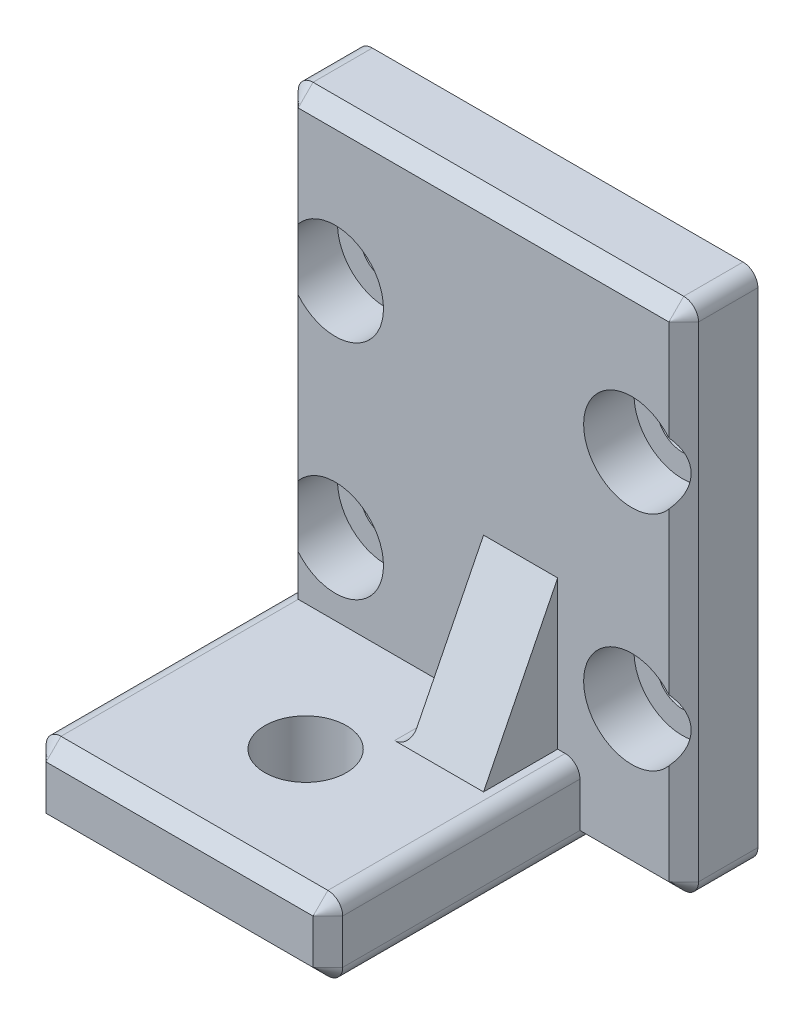
SolidWorks part; units mm, degrees
ref_plane "Front Plane" through (0, 0, 0) normal (0, 0, 1) x (1, 0, 0)
ref_plane "Top Plane" through (0, 0, 0) normal (0, 1, 0) x (1, 0, 0)
ref_plane "Right Plane" through (0, 0, 0) normal (1, 0, 0) x (0, 0, -1)
ref_plane "Rail Mount Front" through (0, 0, 5) normal (0, 0, 1) x (1, 0, 0)
ref_plane "ExtrusionMountFront" through (0, 0, 22) normal (0, 0, 1) x (1, 0, 0)
sketch "RailMountSketch" plane through (0, 0, 0) normal (0, 0, 1) x (1, 0, 0)
  line L1 (-13.5, 0) -> (13.5, 0)
  line L2 (-13.5, 0) -> (-13.5, 34.7)
  line L3 (-13.5, 34.7) -> (13.5, 34.7)
  line L4 (13.5, 0) -> (13.5, 34.7)
  line L5 (-10, 9.85) -> (10, 9.85) construction
  line L6 (-10, 9.85) -> (-10, 24.85) construction
  line L7 (-10, 24.85) -> (10, 24.85) construction
  line L8 (10, 9.85) -> (10, 24.85) construction
  line L9 (-10, 9.85) -> (10, 24.85) construction
  line L10 (-10, 24.85) -> (10, 9.85) construction
  line L11 (-13.5, 5) -> (6.5, 5) construction
  line L12 (-13.5, 5) -> (-13.5, 0) construction
  line L13 (-13.5, 0) -> (6.5, 0) construction
  line L14 (6.5, 5) -> (6.5, 0) construction
  line L15 (-13.5, 5) -> (6.5, 0) construction
  line L16 (-13.5, 0) -> (6.5, 5) construction
  point P4 (0, 17.35)
  point P12 (-3.5, 2.5)
  dimension "D1" = 27
  dimension "D2" = 34.7
  dimension "D3" = 20
  dimension "D4" = 15
  dimension "D5" = 17.35
  dimension "D6" = 20
  dimension "D7" = 6.5
  dimension "D8" = 5
extrude "Rail Mount" add sketch "RailMountSketch" along normal up to surface (5 mm away) up to plane "Rail Mount Front"
ref_plane "ExtrusionMountingTopPlane" through (0, 5, 0) normal (0, 1, 0) x (1, 0, 0)
hole_wizard "Rail Mounting Holes" positions "Sketch2" profile "Sketch3" counterbore size "M3" standard "ISO" end condition through all
sketch "Sketch2" plane through (0, 0, 5) normal (0, 0, 1) x (1, 0, 0)
  point P0 (-10, 24.85)
  point P3 (10, 24.85)
  point P6 (10, 9.85)
  point P9 (-10, 9.85)
sketch "Sketch3" plane through (-10, 24.85, 5) normal (1, 0, 0) x (0, -1, 0)
  line L0 (0, 0) -> (0, 5)
  line L1 (0, 5) -> (1.7, 5)
  line L3 (1.7, 5) -> (1.7, 3.4)
  line L4 (1.7, 3.4) -> (3.25, 3.4)
  line L5 (3.25, 3.4) -> (3.25, 0)
  line L7 (3.25, 0) -> (0, 0)
  line L11 (0, -6.35) -> (0, 107.95) construction
  dimension "Thru Hole Dia." = 3.4
  dimension "Thru Hole Depth" = 5
  dimension "C'Bore Dia." = 6.5
  dimension "C'Bore Depth" = 3.4
sketch "ExtrusionMountSketch" plane through (0, 0, 5) normal (0, 0, 1) x (1, 0, 0)
  line L1 (-13.5, 0) -> (13.5, 0) construction
  line L3 (-13.5, 5) -> (6.5, 5) construction
  line L4 (6.5, 5) -> (6.5, 0)
  line L5 (-13.5, 0) -> (6.5, 0)
  line L6 (-13.5, 5) -> (-13.5, 0)
  line L7 (-13.5, 5) -> (6.5, 5)
extrude "ExtrusionMount" add sketch "ExtrusionMountSketch" along normal up to surface (17 mm away) up to plane "ExtrusionMountFront"
sketch "ExtrusionMountingHolePosition" plane through (0, 5, 0) normal (0, 1, 0) x (1, 0, 0)
  line L0 (-3.5, -22) -> (-3.5, -5)
  line L3 (-13.6459, -5) -> (13.6459, -5) construction
  line L4 (-13.6459, -22) -> (13.6459, -22) construction
  line L5 (-13.5, 0) -> (6.5, 0) construction
  line L6 (-13.5, 0) -> (6.5, 0) construction
  point P0 (-3.5, -13.5)
  point P7 (-3.5, -13.5)
  dimension "D1" = 10
hole_wizard "ExtrusionMountingHole" positions "Sketch8" profile "Sketch9" hole size "M5" standard "ISO" end condition through all
sketch "Sketch8" plane through (0, 5, 0) normal (0, 1, 0) x (1, 0, 0)
  point P0 (-3.5, -13.5)
sketch "Sketch9" plane through (-3.5, 5, 13.5) normal (1, 0, 0) x (0, 0, 1)
  line L0 (0, 0) -> (0, 5)
  line L1 (0, 5) -> (2.75, 5)
  line L2 (2.75, 5) -> (2.75, 0)
  line L5 (2.75, 0) -> (0, 0)
  line L11 (0, -6.35) -> (0, 107.95) construction
  dimension "Thru Hole Dia." = 5.5
  dimension "Thru Hole Depth" = 5
sketch "Webbing Sketch" plane through (0, 0, 0) normal (1, 0, 0) x (0, 0, -1)
  line L1 (-10, 5) -> (-5, 15)
  line L2 (-22, 5) -> (-5, 5) construction
  line L3 (-5, 13.6459) -> (-5, -13.6459) construction
  line L4 (-5, 15) -> (-5, 5)
  line L5 (-5, 5) -> (-10, 5)
  dimension "D1" = 5
  dimension "D2" = 10
extrude "Webbing" add sketch "Webbing Sketch" along normal blind 5
fillet "Print Helper Fillets" radius 1 8 edges at (0, 5, 7.5) (6.5, 5, 13.5) (-13.5, 5, 13.5) (-13.5, 34.7, 2.5) (13.5, 34.7, 2.5) (13.5, 0, 2.5) (6.5, 0, 13.5) (-13.5, 0, 11)
chamfer "Cosmetic Chamfers" distance 1 angle 45 15 edges at (-13.5, 18.85, 5) (-13.2071, 34.4071, 5) (9, 0, 5) (0, 34.7, 5) (13.2071, 0.2929, 5) (13.2071, 34.4071, 5) (13.5, 17.35, 5) (-3.5, 0, 22) (6.2071, 0.2929, 22) (-13.2071, 0.2929, 22) (6.5, 2.5, 22) (-13.5, 2.5, 22) (6.2071, 4.7071, 22) (-13.2071, 4.7071, 22) (-3.5, 5, 22)
sketch "Rail Mounting Holes Positions" plane through (0, 0, 0) normal (0, 0, 1) x (1, 0, 0)
  point P0 (-10, 9.85)
  point P2 (10, 9.85)
  point P4 (10, 24.85)
  point P6 (-10, 24.85)
